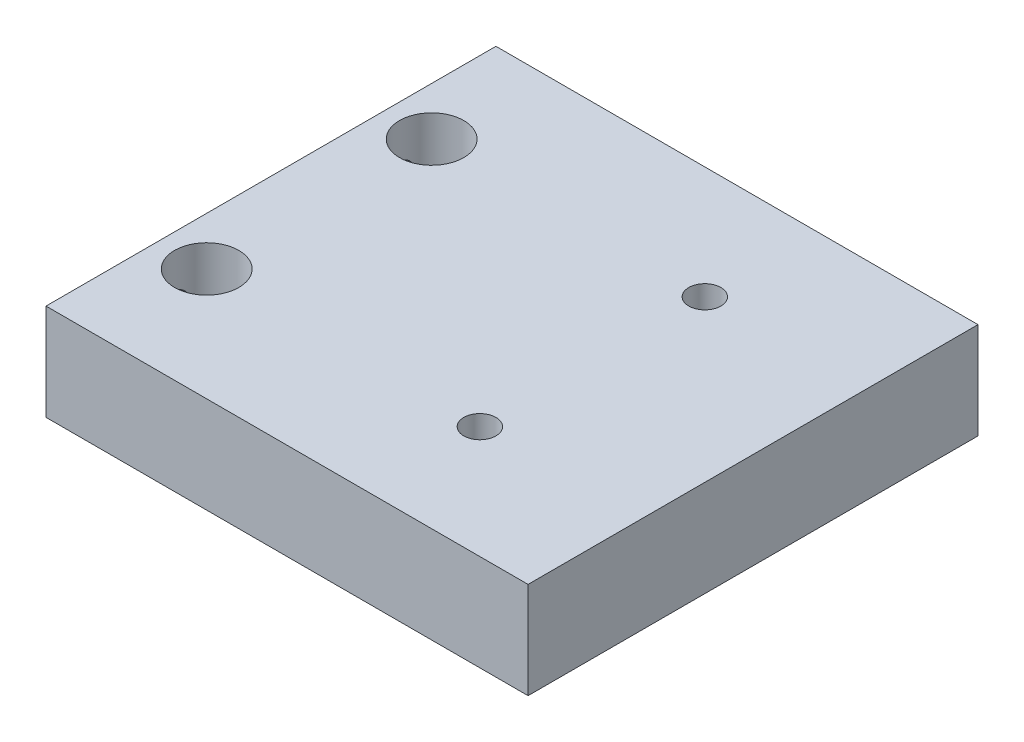
SolidWorks part; units mm, degrees
ref_plane "Front" through (0, 0, 0) normal (0, 0, 1) x (1, 0, 0)
ref_plane "Top" through (0, 0, 0) normal (0, 1, 0) x (1, 0, 0)
ref_plane "Right" through (0, 0, 0) normal (1, 0, 0) x (0, 0, -1)
sketch "Sketch1" plane through (0, 0, 0) normal (0, 1, 0) x (1, 0, 0)
  line L0 (-50, 0) -> (50, 0) construction
  line L1 (-47.625, -44.45) -> (47.625, -44.45)
  line L2 (-47.625, -44.45) -> (-47.625, 44.45)
  line L3 (-47.625, 44.45) -> (47.625, 44.45)
  line L4 (47.625, -44.45) -> (47.625, 44.45)
  line L5 (-47.625, -44.45) -> (47.625, 44.45) construction
  line L6 (-47.625, 44.45) -> (47.625, -44.45) construction
  point P0 (0, 0)
  point P7 (0, 0)
  dimension "D1" = 95.25
  dimension "D2" = 88.9
extrude "Boss-Extrude1" add sketch "Sketch1" along normal mid plane 19.05 contours L3 L4 L1 L2
sketch "Sketch3" plane through (0, 9.525, 0) normal (0, 1, 0) x (1, 0, 0)
  line L0 (-47.625, -44.45) -> (-47.625, 44.45) construction
  line L1 (-38.1, 22.225) -> (-38.1, -22.225) construction
  line L2 (-50, 0) -> (50, 0) construction
  point P0 (-38.1, 22.225)
  point P1 (-38.1, -22.225)
  point P4 (-38.1, 0)
  dimension "D1" = 9.525
  dimension "D2" = 44.45
hole_wizard "1/2 (0.5000) Dowel Hole1" positions "Sketch4" profile "Sketch5" hole size "1/2" standard "ANSI Inch" end condition through all
sketch "Sketch4" plane through (0, 9.525, 0) normal (0, 1, 0) x (1, 0, 0)
  point P0 (-38.1, 22.225)
  point P3 (-38.1, -22.225)
sketch "Sketch5" plane through (-38.1, 9.525, -22.225) normal (1, 0, 0) x (0, 0, 1)
  line L0 (0, 0) -> (0, 19.05)
  line L1 (0, 19.05) -> (6.35, 19.05)
  line L2 (6.35, 19.05) -> (6.35, 0)
  line L5 (6.35, 0) -> (0, 0)
  line L11 (0, -6.35) -> (0, 107.95) construction
  dimension "Thru Hole Dia." = 12.7
  dimension "Thru Hole Depth" = 19.05
sketch "Sketch6" plane through (0, 9.525, 0) normal (0, 1, 0) x (1, 0, 0)
  line L0 (15.875, 22.225) -> (15.875, -22.225) construction
  line L1 (-50, 0) -> (50, 0) construction
  line L2 (47.625, -44.45) -> (47.625, 44.45) construction
  point P0 (15.875, 22.225)
  point P1 (15.875, -22.225)
  point P4 (15.875, 0)
  dimension "D1" = 31.75
hole_wizard "1/4 (0.2500) Dowel Hole1" positions "Sketch7" profile "Sketch8" hole size "1/4" standard "ANSI Inch" end condition through all
sketch "Sketch7" plane through (0, 9.525, 0) normal (0, 1, 0) x (1, 0, 0)
  point P0 (15.875, 22.225)
  point P3 (15.875, -22.225)
sketch "Sketch8" plane through (15.875, 9.525, -22.225) normal (1, 0, 0) x (0, 0, 1)
  line L0 (0, 0) -> (0, 19.05)
  line L1 (0, 19.05) -> (3.175, 19.05)
  line L2 (3.175, 19.05) -> (3.175, 0)
  line L5 (3.175, 0) -> (0, 0)
  line L11 (0, -6.35) -> (0, 107.95) construction
  dimension "Thru Hole Dia." = 6.35
  dimension "Thru Hole Depth" = 19.05
sketch "Sketch9" plane through (-47.625, 0, 0) normal (-1, 0, 0) x (0, 0, 1)
  line L0 (-22.225, 0) -> (22.225, 0) construction
  line L1 (0, -50) -> (0, 50) construction
  line L2 (50, 0) -> (-50, 0) construction
  point P0 (-22.225, 0)
  point P1 (22.225, 0)
  point P2 (0, 0)
hole_wizard "1/4-20 Tapped Hole1" positions "Sketch10" profile "Sketch12" tap size "1/4-20" standard "ANSI Inch" end condition up to next
sketch "Sketch10" plane through (-47.625, 0, 0) normal (-1, 0, 0) x (0, 0, 1)
  point P0 (-22.225, 0)
  point P3 (22.225, 0)
sketch "Sketch12" plane through (-47.625, 0, -22.225) normal (0, 1, 0) x (0, 0, 1)
  line L0 (0, 0) -> (0, 3.175)
  line L1 (0, 3.175) -> (2.5527, 3.175)
  line L2 (2.5527, 3.175) -> (2.5527, 0)
  line L5 (2.5527, 0) -> (0, 0)
  line L11 (0, -6.35) -> (0, 107.95) construction
  dimension "Thru Tap Drill Dia." = 5.1054
  dimension "Thru Tap Drill Depth" = 3.175
cosmetic thread "Hole Thread1" parameters "D2"=6.35
cosmetic thread "Hole Thread2" parameters "D2"=6.35
